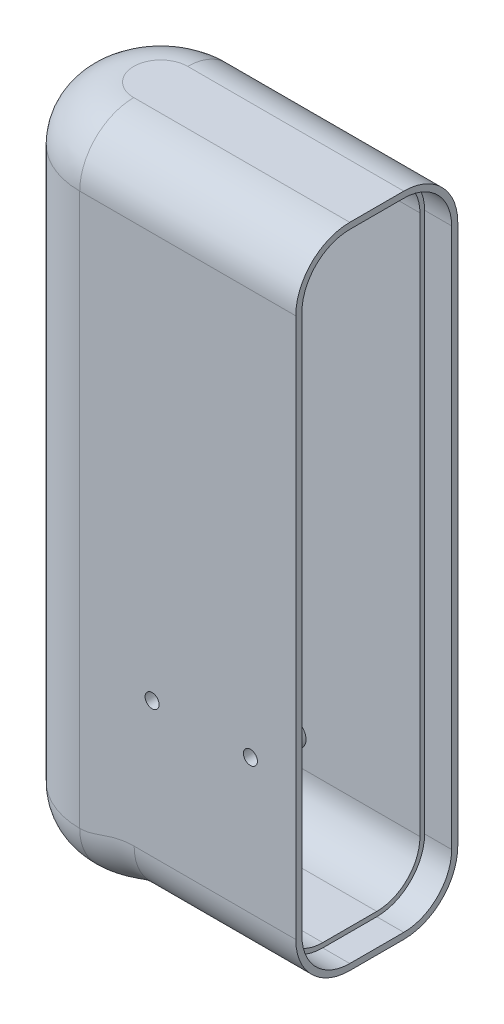
SolidWorks part; units mm, degrees
ref_plane "Front Plane" through (0, 0, 0) normal (0, 0, 1) x (1, 0, 0)
ref_plane "Top Plane" through (0, 0, 0) normal (0, 1, 0) x (1, 0, 0)
ref_plane "Right Plane" through (0, 0, 0) normal (1, 0, 0) x (0, 0, -1)
sketch "Sketch1" plane through (0, 0, 0) normal (0, 1, 0) x (1, 0, 0)
  line L0 (0, 19.05) -> (50.8, 19.05)
  line L1 (50.8, 19.05) -> (50.8, -19.05)
  line L2 (50.8, -19.05) -> (0, -19.05)
  arc A0 (0, 19.05) -> (0, -19.05) centre (0, 0) ccw
  dimension "D1" = 38.1
  dimension "D2" = 50.8
extrude "Boss-Extrude1" add sketch "Sketch1" along normal mid plane 152.4
sketch "Sketch2" plane through (0, -76.2, 0) normal (0, -1, 0) x (1, 0, 0)
  circle A0 centre (0, 0) radius 14.2875
  dimension "D1" = 28.575
extrude "Cut-Extrude1" cut sketch "Sketch2" against normal blind 114.3
fillet "Fillet1" radius 12.7 5 edges at (25.4, 76.2, -19.05) (25.4, 76.2, 19.05) (25.4, -76.2, -19.05) (25.4, -76.2, 19.05) (-19.05, 76.2, 0)
sketch "Sketch3" plane through (50.8, 0, 0) normal (1, 0, 0) x (0, 0, -1)
  line L8 (16.51, -63.5) -> (16.51, 63.5)
  line L9 (6.35, 73.66) -> (-6.35, 73.66)
  line L10 (-16.51, 63.5) -> (-16.51, -63.5)
  line L11 (-6.35, -73.66) -> (6.35, -73.66)
  line L12 (16.51, -63.5) -> (16.51, 63.5)
  line L13 (6.35, 73.66) -> (-6.35, 73.66)
  line L14 (-16.51, 63.5) -> (-16.51, -63.5)
  line L15 (-6.35, -73.66) -> (6.35, -73.66)
  arc A8 (16.51, 63.5) -> (6.35, 73.66) centre (6.35, 63.5) ccw
  arc A9 (-6.35, 73.66) -> (-16.51, 63.5) centre (-6.35, 63.5) ccw
  arc A10 (-16.51, -63.5) -> (-6.35, -73.66) centre (-6.35, -63.5) ccw
  arc A11 (6.35, -73.66) -> (16.51, -63.5) centre (6.35, -63.5) ccw
  arc A12 (16.51, 63.5) -> (6.35, 73.66) centre (6.35, 63.5) ccw
  arc A13 (-6.35, 73.66) -> (-16.51, 63.5) centre (-6.35, 63.5) ccw
  arc A14 (-16.51, -63.5) -> (-6.35, -73.66) centre (-6.35, -63.5) ccw
  arc A15 (6.35, -73.66) -> (16.51, -63.5) centre (6.35, -63.5) ccw
  dimension "D1" = 2.54
extrude "Cut-Extrude2" cut sketch "Sketch3" against normal blind 44.45
sketch "Sketch4" plane through (0, 38.1, 0) normal (0, -1, 0) x (1, 0, 0)
  line L1 (3.81, 11.1125) -> (6.35, 11.1125)
  line L2 (3.81, -11.1125) -> (3.81, 11.1125)
  line L5 (6.35, -12.7988) -> (6.35, 12.7988) construction
  line L6 (3.81, -11.1125) -> (6.35, -11.1125)
  line L7 (6.35, -11.1125) -> (6.35, 11.1125)
  arc A2 (3.81, 11.1125) -> (3.81, -11.1125) centre (0, 0) ccw
  arc A3 (3.81, 11.1125) -> (3.81, -11.1125) centre (0, 0) ccw
  dimension "D1" = 2.54
extrude "Cut-Extrude3" cut sketch "Sketch4" against normal blind 31.75
sketch "Sketch6" plane through (50.8, 0, 0) normal (1, 0, 0) x (0, 0, -1)
  line L0 (-17.5992, 63.5) -> (-17.5992, -63.5)
  line L1 (-6.35, -74.7492) -> (6.35, -74.7492)
  line L2 (17.5992, -63.5) -> (17.5992, 63.5)
  line L3 (6.35, 74.7492) -> (-6.35, 74.7492)
  line L4 (19.05, -63.5) -> (19.05, 63.5)
  line L5 (6.35, 76.2) -> (-6.35, 76.2)
  line L6 (-19.05, 63.5) -> (-19.05, -63.5)
  line L7 (-6.35, -76.2) -> (6.35, -76.2)
  line L8 (19.05, -63.5) -> (19.05, 63.5) construction
  line L9 (6.35, 76.2) -> (-6.35, 76.2) construction
  line L10 (-19.05, 63.5) -> (-19.05, -63.5) construction
  line L11 (-6.35, -76.2) -> (6.35, -76.2) construction
  arc A0 (-6.35, 74.7492) -> (-17.5992, 63.5) centre (-6.35, 63.5) ccw
  arc A1 (-17.5992, -63.5) -> (-6.35, -74.7492) centre (-6.35, -63.5) ccw
  arc A2 (6.35, -74.7492) -> (17.5992, -63.5) centre (6.35, -63.5) ccw
  arc A3 (17.5992, 63.5) -> (6.35, 74.7492) centre (6.35, 63.5) ccw
  arc A4 (19.05, 63.5) -> (6.35, 76.2) centre (6.35, 63.5) ccw
  arc A5 (-6.35, 76.2) -> (-19.05, 63.5) centre (-6.35, 63.5) ccw
  arc A6 (-19.05, -63.5) -> (-6.35, -76.2) centre (-6.35, -63.5) ccw
  arc A7 (6.35, -76.2) -> (19.05, -63.5) centre (6.35, -63.5) ccw
  arc A8 (19.05, 63.5) -> (6.35, 76.2) centre (6.35, 63.5) ccw construction
  arc A9 (-6.35, 76.2) -> (-19.05, 63.5) centre (-6.35, 63.5) ccw construction
  arc A10 (-19.05, -63.5) -> (-6.35, -76.2) centre (-6.35, -63.5) ccw construction
  arc A11 (6.35, -76.2) -> (19.05, -63.5) centre (6.35, -63.5) ccw construction
  dimension "D1" = 0
  dimension "D2" = 1.4508
extrude "Cut-Extrude4" cut sketch "Sketch6" against normal blind 6.35
sketch "Sketch8" plane through (0, 0, 16.51) normal (0, 0, -1) x (-1, 0, 0)
  line L0 (-6.35, 63.5) -> (-6.35, -63.5) construction
  line L2 (-6.35, 63.5) -> (-6.35, -63.5) construction
  line L3 (-50.8, 63.5) -> (-50.8, -63.5) construction
  line L4 (-6.35, -31.75) -> (-50.8, -31.75) construction
  line L5 (-50.8, -76.2) -> (-12.7988, -76.2) construction
  line L6 (-28.575, -31.75) -> (-28.575, 49968.25) construction
  line L7 (-50.8, 63.5) -> (-50.8, -63.5) construction
  circle A0 centre (-17.018, -31.75) radius 1.651
  circle A1 centre (-40.132, -31.75) radius 1.651
  point P14 (-28.575, -31.75)
  dimension "D3" = 3.302
  dimension "D1" = 44.45
  dimension "D2" = 23.114
extrude "Cut-Extrude6" cut sketch "Sketch8" against normal through all
sketch "Sketch9" plane through (0, 0, 19.05) normal (0, 0, 1) x (1, 0, 0)
  circle A0 centre (40.132, -31.75) radius 1.651 construction
  circle A1 centre (17.018, -31.75) radius 1.651 construction
  circle A2 centre (40.132, -31.75) radius 1.651
  circle A3 centre (17.018, -31.75) radius 1.651
extrude "Extrude-Thin1" add sketch "Sketch9" against normal blind 10.16 thin
sketch "Sketch10" plane through (0, 0, 8.89) normal (0, 0, -1) x (-1, 0, 0)
  line L1 (-40.132, -28.829) -> (-17.018, -28.829)
  line L2 (-40.132, -28.829) -> (-40.132, -34.671)
  line L3 (-40.132, -34.671) -> (-17.018, -34.671)
  line L4 (-17.018, -28.829) -> (-17.018, -34.671)
  circle A0 centre (-40.132, -31.75) radius 2.921 construction
  circle A1 centre (-17.018, -31.75) radius 2.921 construction
extrude "Cut-Extrude7" cut sketch "Sketch10" against normal blind 2.54
